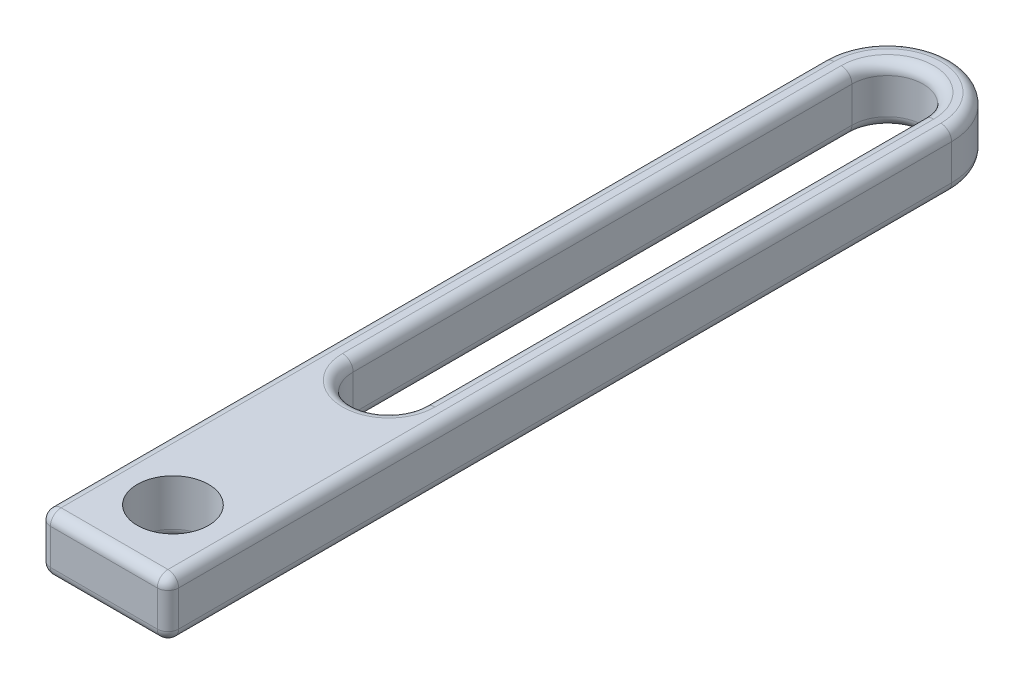
SolidWorks part; units mm, degrees
ref_plane "Front Plane" through (0, 0, 0) normal (0, 0, 1) x (1, 0, 0)
ref_plane "Top Plane" through (0, 0, 0) normal (0, 1, 0) x (1, 0, 0)
ref_plane "Right Plane" through (0, 0, 0) normal (1, 0, 0) x (0, 0, -1)
sketch "Sketch1" plane through (0, 0, 0) normal (0, 1, 0) x (1, 0, 0)
  line L0 (0, -17.5) -> (0, 17.5) construction
  line L1 (-2.5, -17.5) -> (-2.5, 17.5)
  line L2 (2.5, -17.5) -> (2.5, 17.5)
  line L3 (-4.5, -17.5) -> (-4.5, 17.5)
  line L4 (4.5, -17.5) -> (4.5, 17.5)
  line L5 (-4.5, -17.5) -> (-4.5, -37.5)
  line L6 (-4.5, -37.5) -> (4.5, -37.5)
  line L7 (4.5, -37.5) -> (4.5, -17.5)
  arc A0 (-2.5, -17.5) -> (2.5, -17.5) centre (0, -17.5) ccw
  arc A1 (2.5, 17.5) -> (-2.5, 17.5) centre (0, 17.5) ccw
  arc A2 (4.5, 17.5) -> (-4.5, 17.5) centre (0, 17.5) ccw
  arc A4 (-4.5, -17.5) -> (4.5, -17.5) centre (0, -17.5) ccw construction
  circle A5 centre (0, -32.6492) radius 2.5
  point P3 (0, 0)
  dimension "D1" = 35
  dimension "D2" = 2.5
  dimension "D4" = 20
  dimension "D3" = 2
extrude "Boss-Extrude1" add sketch "Sketch1" along normal blind 4
fillet "Fillet1" radius 0.75 19 edges at (-4.5, 4, 10) (-4.5, 2, 37.5) (0, 4, 37.5) (-2.5, 0, 0) (0, 0, -20) (2.5, 0, 0) (0, 0, 20) (-4.5, 0, 10) (0, 0, 37.5) (0, 4, -22) (0, 0, -22) (4.5, 2, 37.5) (4.5, 4, 10) (4.5, 0, 10) (0, 4, 20) (-2.5, 4, 0) (0, 4, -20) (2.5, 4, 0) (0, 0, 35.1492)
